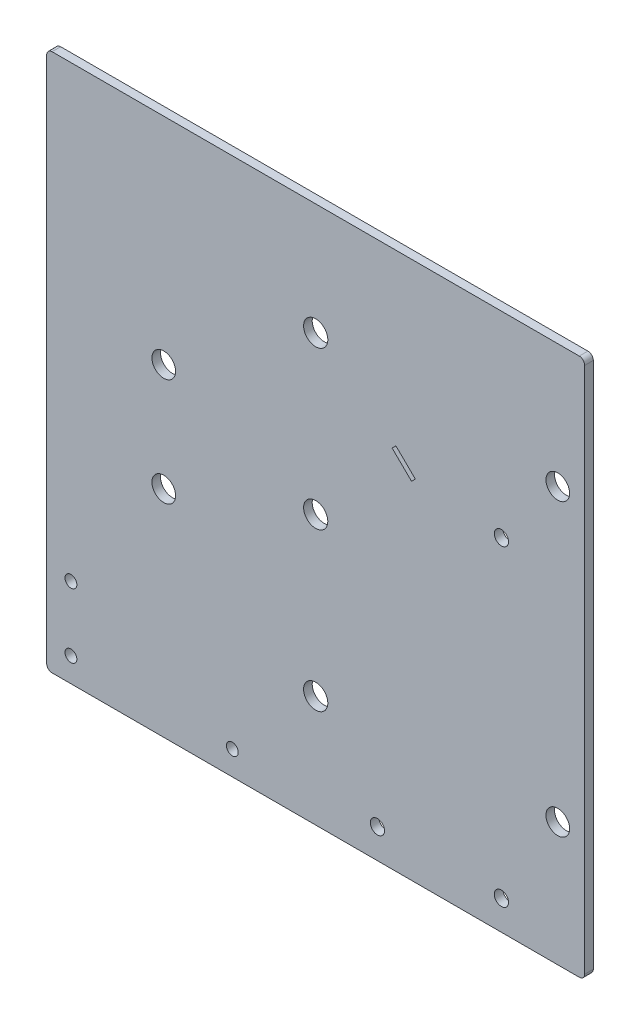
SolidWorks part; units mm, degrees
material "FR4_stuffedProtoboard"
ref_plane "Front Plane" through (0, 0, 0) normal (0, 0, 1) x (1, 0, 0)
ref_plane "Top Plane" through (0, 0, 0) normal (0, 1, 0) x (1, 0, 0)
ref_plane "Right Plane" through (0, 0, 0) normal (1, 0, 0) x (0, 0, -1)
sketch "Sketch1" plane through (0, 0, 0) normal (0, 0, 1) x (1, 0, 0)
  line L1 (-50, -50) -> (50, -50)
  line L2 (-50, -50) -> (-50, 50)
  line L3 (-50, 50) -> (50, 50)
  line L4 (50, -50) -> (50, 50)
  line L5 (-50, -50) -> (50, 50) construction
  line L6 (-50, 50) -> (50, -50) construction
  dimension "D1" = 100
extrude "Boss-Extrude1" add sketch "Sketch1" along normal blind 1.6
sketch "Sketch2" [suppressed] plane through (0, 0, 1.6) normal (0, 0, 1) x (1, 0, 0)
  circle A0 centre (0, 0) radius 50
  line M2 (50, -50) -> (50, 50)
  line M3 (50, 50) -> (-50, 50)
  line M4 (-50, 50) -> (-50, -50)
  line M5 (-50, -50) -> (50, -50)
  dimension "D1" = 100
extrude "Cut-Extrude1" [suppressed] cut sketch "Sketch2" against normal blind 1.6 contours A0 M3 M4 | A0 M4 M5 | A0 M5 M2 | A0 M2 M3
sketch "Sketch3" plane through (0, 0, 1.6) normal (0, 0, -1) x (-1, 0, 0)
  line L0 (-40, -22) -> (-50, -22) construction
  line L1 (-40, -32) -> (-40, -22) construction
  line L2 (-50, -32) -> (-40, -32) construction
  line L3 (-50, -22) -> (-50, -32) construction
  line L4 (-40, -22) -> (-50, -22)
  line L5 (-40, -32) -> (-40, -22)
  line L6 (-50, -32) -> (-40, -32)
  line L7 (-50, -22) -> (-50, -32)
  line L8 (-40, 22) -> (-40, 32) construction
  line L9 (-40, 32) -> (-50, 32) construction
  line L10 (-50, 32) -> (-50, 22) construction
  line L11 (-50, 22) -> (-40, 22) construction
  line L12 (-40, 22) -> (-40, 32)
  line L13 (-40, 32) -> (-50, 32)
  line L14 (-50, 32) -> (-50, 22)
  line L15 (-50, 22) -> (-40, 22)
  line L32 (17.2447, 25) -> (45.2447, 25) construction
  line L33 (45.2447, 25) -> (45.2447, -25) construction
  line L34 (17.2447, -25) -> (45.2447, -25) construction
  line L35 (17.2447, 25) -> (17.2447, -25) construction
  line L36 (17.2447, 25) -> (45.2447, 25)
  line L37 (45.2447, 25) -> (45.2447, -25)
  line L38 (17.2447, -25) -> (45.2447, -25)
  line L39 (17.2447, 25) -> (17.2447, -25)
  circle A3 centre (0, 0) radius 2.2479
  circle A4 centre (-34.525, -44.525) radius 1.325 construction
  circle A6 centre (-34.525, -44.525) radius 1.325
  circle A10 centre (0, -29.25) radius 2.25
  circle A11 centre (-45, -27) radius 2.2
  circle A12 centre (0, 29.25) radius 2.25
  circle A13 centre (-45, 27) radius 2.2
  circle A14 centre (-34.525, 13.525) radius 1.325 construction
  circle A15 centre (-34.525, 13.525) radius 1.325
  circle A16 centre (15.5, -45.5) radius 1.1 construction
  circle A17 centre (15.5, -45.5) radius 1.1
  circle A18 centre (45.5, -45.5) radius 1.1 construction
  circle A19 centre (45.5, -45.5) radius 1.1
  circle A20 centre (45.5, -33.5) radius 1.1 construction
  circle A21 centre (45.5, -33.5) radius 1.1
  circle A22 centre (-11.475, -44.525) radius 1.325 construction
  circle A23 centre (-11.475, -44.525) radius 1.325
  circle A25 centre (28.2447, -9.9994) radius 2.2
  circle A27 centre (28.2447, 10.0006) radius 2.2
  circle A28 centre (-45, 27) radius 2.2 construction
  circle A29 centre (-45, 27) radius 2.2
  circle A30 centre (-45, -27) radius 2.2 construction
  circle A31 centre (-45, -27) radius 2.2
  dimension "D1" = 4.4958
extrude "Cut-Extrude2" cut sketch "Sketch3" along normal through all contours A13 | A11 | A3 | A15 | A6 | A23 | A27 | A25 | A17 | A21 | A19 | A12 | A10 region at (0, 0, 1.6) region at (34.525, -44.525, 1.6) region at (45, -27, 1.6) region at (45, 27, 1.6) region at (34.525, 13.525, 1.6) region at (-15.5, -45.5, 1.6) region at (-45.5, -45.5, 1.6) region at (-45.5, -33.5, 1.6) region at (11.475, -44.525, 1.6) region at (-28.2447, -9.9994, 1.6) region at (-28.2447, 10.0006, 1.6)
sketch "Sketch4" plane through (0, 0, 1.6) normal (0, 0, 1) x (1, 0, 0)
  line L0 (38, -44.25) -> (38, -18.925) construction
  line L5 (38, -44.25) -> (38, -18.925)
  line L6 (11.75, -48) -> (34.25, -48) construction
  line L7 (11.75, -48) -> (34.25, -48)
  line L8 (8, -44.25) -> (8, 13.25) construction
  line L9 (8, -44.25) -> (8, 13.25)
  line L11 (33, -3) -> (33, -48) construction
  line L13 (34.25, 17) -> (11.75, 17)
  line L14 (38, 13.25) -> (38, -18.925)
  line L15 (-48, -48) -> (-13, -48) construction
  line L16 (-48, -48) -> (-13, -48)
  line L17 (-48, -31) -> (-48, -48) construction
  line L18 (-48, -31) -> (-48, -48)
  line L19 (-13, -40.5) -> (-13, -32.5) construction
  line L20 (-13, -40.5) -> (-13, -32.5)
  line L21 (-13, -48) -> (-13, -40.5) construction
  line L22 (-13, -48) -> (-13, -40.5)
  line L23 (-13, -32.5) -> (-13, -31) construction
  line L24 (-13, -32.5) -> (-13, -31)
  line L25 (-13, -31) -> (-48, -31) construction
  line L26 (-13, -31) -> (-48, -31)
  line L27 (-20, -34) -> (-20, -48) construction
  arc A0 (34.25, -48) -> (38, -44.25) centre (34.25, -44.25) ccw construction
  arc A1 (34.25, -48) -> (38, -44.25) centre (34.25, -44.25) ccw
  arc A2 (8, -44.25) -> (11.75, -48) centre (11.75, -44.25) ccw construction
  arc A3 (8, -44.25) -> (11.75, -48) centre (11.75, -44.25) ccw
  arc A4 (11.75, 17) -> (8, 13.25) centre (11.75, 13.25) ccw construction
  arc A5 (11.75, 17) -> (8, 13.25) centre (11.75, 13.25) ccw
  arc A6 (38, 13.25) -> (34.25, 17) centre (34.25, 13.25) ccw construction
  arc A7 (38, 13.25) -> (34.25, 17) centre (34.25, 13.25) ccw
  text T0 "Raspberry Pi Zero W" font "Century Gothic" height 2
  text T1 "Atheros" font "Century Gothic" height 2
  dimension "D1" = 5
  dimension "D2" = 20
  dimension "D3" = 3
  dimension "D4" = 7
fillet "Fillet1" radius 1 4 edges at (-50, -50, 0.8) (-50, 50, 0.8) (50, -50, 0.8) (50, 50, 0.8)
sketch "Sketch5" plane through (0, 0, 0) normal (0, 0, -1) x (-1, 0, 0)
  line L16 (-14.2075, 17.7955) -> (-17.8185, 14.2525)
  line L17 (-17.8185, 14.2525) -> (-18.5188, 14.9663)
  line L18 (-18.5188, 14.9663) -> (-14.9078, 18.5093)
  line L19 (-14.9078, 18.5093) -> (-14.2075, 17.7955)
  line L20 (-16.7133, 16.7378) -> (-13.0663, 13.0208) construction
  spline S1 degree 3 poles (-15.4367, 15.4367) (-16.4808, 14.8306) (-17.4743, 14.1392) (-18.4059, 13.3713) knots 0 0 0 0 1 1 1 1 construction
extrude "Cut-Extrude4" cut sketch "Sketch5" against normal through all contours L18 L19 L16 L17
